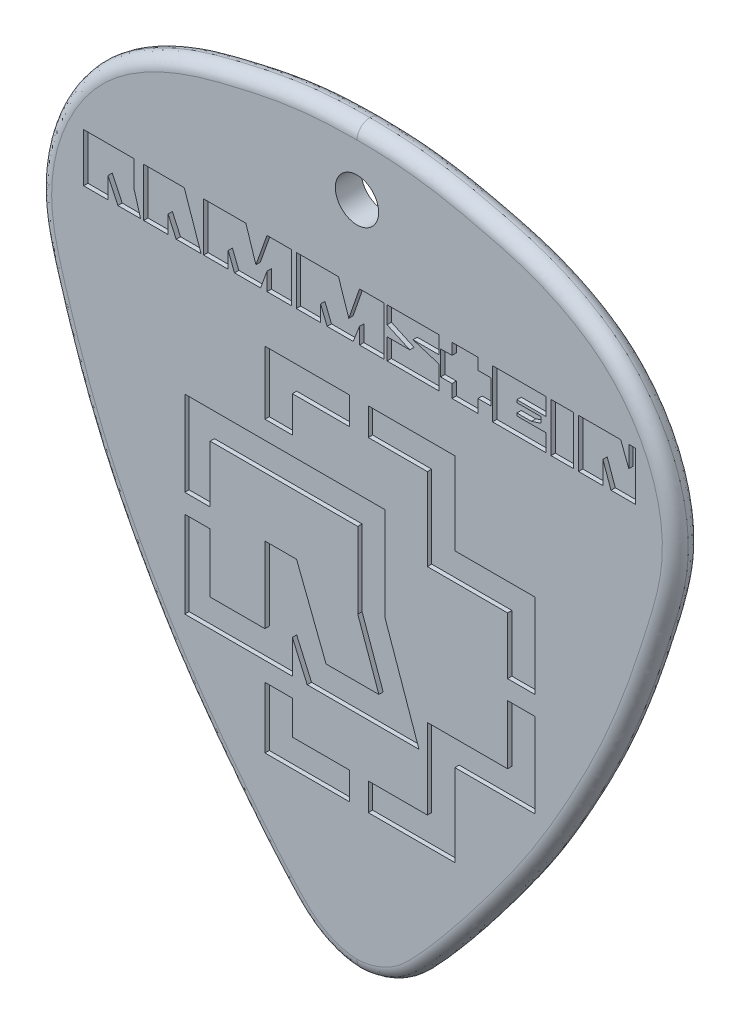
SolidWorks part; units mm, degrees
material "Nickel"
ref_plane "Front Plane" through (0, 0, 0) normal (0, 0, 1) x (1, 0, 0)
ref_plane "Top Plane" through (0, 0, 0) normal (0, 1, 0) x (1, 0, 0)
ref_plane "Right Plane" through (0, 0, 0) normal (1, 0, 0) x (0, 0, -1)
sketch "Sketch9" plane through (-49.9652, -1.9798, 0) normal (0, 0, 1) x (1, 0, 0)
  line L0 (49.9312, 18.5668) -> (49.9312, -17.1079) construction
  circle A1 centre (49.9312, 15.0287) radius 1
  spline S0 degree 3 poles (49.9312, 18.0287) (50.5822, 18.0238) (52.0435, 17.9887) (54.0305, 17.7033) (55.988, 17.2529) (58.0088, 16.7337) (60.0094, 15.8622) (62.6561, 14.0289) (64.4616, 11.0538) (64.7875, 7.3749) (63.9283, 4.4589) (62.9446, 1.4332) (61.7117, -1.5745) (60.1785, -4.5073) (58.5607, -7.295) (56.6435, -9.9646) (54.8628, -12.2747) (53.3893, -13.9945) (51.9899, -15.4429) (50.7935, -15.9421) (49.9312, -15.9653) knots 0 0 0 0 0.039894 0.08945 0.122624 0.162957 0.217169 0.255208 0.359361 0.416146 0.477175 0.543509 0.611614 0.675829 0.746189 0.80884 0.877031 0.924799 0.947638 1 1 1 1
  spline S1 degree 3 poles (49.9312, 18.0287) (49.2802, 18.0238) (47.819, 17.9887) (45.832, 17.7033) (43.8744, 17.2529) (41.8537, 16.7337) (39.853, 15.8622) (37.2063, 14.0289) (35.4008, 11.0538) (35.075, 7.3749) (35.9342, 4.4589) (36.9178, 1.4332) (38.1507, -1.5745) (39.684, -4.5073) (41.3018, -7.295) (43.219, -9.9646) (44.9997, -12.2747) (46.4731, -13.9945) (47.8725, -15.4429) (49.0689, -15.9421) (49.9312, -15.9653) knots 0 0 0 0 0.039894 0.08945 0.122624 0.162957 0.217169 0.255208 0.359361 0.416146 0.477175 0.543509 0.611614 0.675829 0.746189 0.80884 0.877031 0.924799 0.947638 1 1 1 1
  dimension "D1" = 2
  dimension "D2" = 3
extrude "mediator_2" add sketch "Sketch9" against normal blind 1.2 separate body
sketch "Sketch10" plane through (-49.9652, -1.9798, 0) normal (0, 0, 1) x (1, 0, 0)
  line L78 (101.711, 196.2021) -> (368.3776, 196.2021) construction
  line L79 (39.6213, 11.5287) -> (39.6213, 10.3368)
  line L80 (37.2943, 9.2785) -> (38.419, 9.2785)
  line L81 (37.2943, 9.2785) -> (37.2943, 11.5287)
  line L82 (37.2943, 11.5287) -> (39.6213, 11.5287)
  line L83 (62.7948, 9.2785) -> (62.7948, 11.5287)
  line L84 (39.6213, 10.3368) -> (39.9259, 9.2785)
  line L85 (38.419, 9.2785) -> (38.419, 10.2495)
  line L86 (38.419, 10.2495) -> (38.8771, 9.2785)
  line L87 (38.8771, 9.2785) -> (39.9259, 9.2785)
  line L88 (40.0704, 9.2785) -> (40.0704, 11.5287)
  line L89 (40.0704, 11.5287) -> (41.9447, 11.5287)
  line L90 (40.0704, 9.2785) -> (41.1994, 9.2785)
  line L91 (41.1994, 9.2785) -> (41.1994, 10.0986)
  line L92 (41.1994, 10.0986) -> (41.5727, 9.2785)
  line L93 (41.5727, 9.2785) -> (42.7203, 9.2785)
  line L94 (41.9447, 11.5287) -> (42.7203, 9.2785)
  line L95 (42.8452, 11.5287) -> (42.8452, 9.2785)
  line L96 (42.8452, 9.2785) -> (43.9744, 9.2785)
  line L97 (42.8452, 11.5287) -> (44.794, 11.5287)
  line L98 (46.8969, 11.5287) -> (46.8969, 9.2785)
  line L99 (47.1236, 9.2785) -> (47.1236, 11.5287)
  line L100 (47.1236, 11.5287) -> (49.0768, 11.5287)
  line L101 (47.1236, 9.2785) -> (48.2472, 9.2785)
  line L102 (51.1763, 11.5287) -> (51.1763, 9.2785)
  line L103 (51.3206, 9.2785) -> (51.3206, 10.2495)
  line L104 (51.3206, 11.5287) -> (53.725, 11.5287)
  line L105 (51.3206, 9.2785) -> (53.725, 9.2785)
  line L106 (53.725, 11.5287) -> (53.725, 10.7287)
  line L107 (55.52, 11.0032) -> (55.52, 11.5287)
  line L108 (53.7944, 11.0032) -> (54.3202, 11.0032)
  line L109 (53.7944, 11.0032) -> (53.7944, 9.8774)
  line L110 (53.7944, 9.8774) -> (54.3202, 9.8774)
  line L111 (56.1212, 11.0032) -> (56.1212, 9.8774)
  line L112 (54.3202, 9.2785) -> (55.52, 9.2785)
  line L113 (54.3202, 9.2785) -> (54.3202, 9.8774)
  line L114 (54.3202, 11.5287) -> (55.52, 11.5287)
  line L115 (55.52, 9.2785) -> (55.52, 9.8774)
  line L116 (54.3202, 11.0032) -> (54.3202, 11.5287)
  line L117 (55.52, 11.0032) -> (56.1212, 11.0032)
  line L118 (55.52, 9.8774) -> (56.1212, 9.8774)
  line L119 (54.3202, 11.5287) -> (55.52, 11.5287)
  line L120 (54.3202, 9.2785) -> (55.52, 9.2785)
  line L121 (43.9744, 9.2785) -> (43.9744, 10.0267)
  line L122 (43.9744, 10.0267) -> (44.2682, 9.2785)
  line L123 (45.7696, 9.2785) -> (45.7696, 10.0986)
  line L124 (45.7696, 10.0986) -> (45.4724, 9.2785)
  line L125 (44.2682, 9.2785) -> (45.4724, 9.2785)
  line L126 (45.7696, 9.2785) -> (46.8969, 9.2785)
  line L127 (44.794, 11.5287) -> (45.2581, 10.0986)
  line L128 (45.2581, 10.0986) -> (45.7696, 11.5287)
  line L129 (45.7696, 11.5287) -> (46.8969, 11.5287)
  line L130 (49.0768, 11.5287) -> (49.5501, 10.0986)
  line L131 (49.5501, 10.0986) -> (50.0466, 11.5287)
  line L132 (50.0466, 11.5287) -> (51.1763, 11.5287)
  line L133 (48.2472, 9.2785) -> (48.2472, 10.0267)
  line L134 (48.2472, 10.0267) -> (48.55, 9.2785)
  line L135 (48.55, 9.2785) -> (49.7528, 9.2785)
  line L136 (50.0466, 9.2785) -> (50.0466, 10.0267)
  line L137 (50.0466, 10.0267) -> (49.7528, 9.2785)
  line L138 (50.0466, 9.2785) -> (51.1763, 9.2785)
  line L139 (51.3206, 10.2495) -> (52.3702, 10.2495)
  line L140 (52.3702, 10.2495) -> (51.3206, 10.7287)
  line L141 (51.3206, 10.7287) -> (51.3206, 11.5287)
  line L142 (53.725, 10.7287) -> (52.5197, 10.7287)
  line L143 (52.5197, 10.7287) -> (53.725, 10.3544)
  line L144 (53.725, 10.3544) -> (53.725, 9.2785)
  line L145 (56.1952, 11.5287) -> (56.1952, 9.2785)
  line L146 (56.1952, 11.5287) -> (58.6695, 11.5287)
  line L147 (56.1952, 9.2785) -> (58.6695, 9.2785)
  line L148 (58.6695, 11.5287) -> (58.6695, 10.7287)
  line L149 (58.6695, 10.7287) -> (57.3202, 10.7287)
  line L150 (57.3202, 10.7287) -> (57.3202, 10.6087)
  line L151 (57.3202, 10.6087) -> (58.4448, 10.6087)
  line L152 (58.4448, 10.6087) -> (58.4448, 10.3486)
  line L153 (58.4448, 10.3486) -> (57.9949, 10.1985)
  line L154 (57.9949, 10.1985) -> (57.3189, 10.1985)
  line L155 (57.3189, 10.1985) -> (57.3189, 10.0785)
  line L156 (57.3189, 10.0785) -> (58.6695, 10.0785)
  line L157 (58.6695, 10.0785) -> (58.6695, 9.2785)
  line L158 (58.8938, 11.5287) -> (58.8938, 9.2785)
  line L159 (59.9445, 11.5287) -> (59.9445, 9.2785)
  line L160 (58.8938, 9.2785) -> (59.9445, 9.2785)
  line L161 (58.8938, 11.5287) -> (59.9445, 11.5287)
  line L162 (60.1688, 11.5287) -> (60.1688, 9.2785)
  line L163 (60.1688, 9.2785) -> (61.2951, 9.2785)
  line L164 (60.1688, 11.5287) -> (62.119, 11.5287)
  line L165 (62.4942, 11.5287) -> (62.4942, 10.5531)
  line L166 (62.4942, 10.5531) -> (62.119, 11.5287)
  line L167 (62.4942, 11.5287) -> (62.7948, 11.5287)
  line L168 (61.2951, 9.2785) -> (61.2951, 10.3281)
  line L169 (61.2951, 10.3281) -> (61.6698, 9.2785)
  line L170 (61.6698, 9.2785) -> (62.7948, 9.2785)
  circle A0 centre (49.9312, 15.0287) radius 1 construction
  dimension "D1" = 3.5
  dimension "D2" = 0.8
  dimension "D3" = 0.8
  dimension "D4" = 0.12
  dimension "D5" = 0.12
fillet "Fillet3" radius 0.6 4 edges
extrude "Rammstein" cut sketch "Sketch10" against normal blind 0.2 contours L86 L87 L84 L79 L82 L81 L80 L85 | L94 L89 L88 L90 L91 L92 L93 | L129 L128 L127 L97 L95 L96 L121 L122 L125 L124 L123 L126 L98 | L136 L138 L102 L132 L131 L130 L100 L99 L101 L133 L134 L135 L137 | L144 L143 L142 L106 L104 L141 L140 L139 L103 L105 | L115 L118 L111 L117 L107 L114 L116 L108 L109 L110 L113 L112 | L157 L156 L155 L154 L153 L152 L151 L150 L149 L148 L146 L145 L147 | L169 L170 L83 L167 L165 L166 L164 L162 L163 L168 | L158 L160 L159 L161 region at (-11.4729, 8.4341, 0) region at (11.4894, 8.4248, 0) region at (-8.7561, 8.3839, 0) region at (-5.1297, 8.3929, 0) region at (-0.8494, 8.3928, 0) region at (2.5644, 8.4143, 0) region at (4.9798, 8.4355, 0) region at (7.4056, 8.4248, 0)
sketch "Sketch11" plane through (0, 0, 0) normal (0, 0, 1) x (1, 0, 0)
  line L0 (25.7842, 90.0176) -> (159.1175, 90.0176) construction
  line L17 (-0.3902, 3.8019) -> (-3.0225, 3.8019)
  line L18 (-4.2901, 2.1447) -> (-3.0225, 2.1447)
  line L19 (-4.2901, 2.1447) -> (-4.2901, 5.0698)
  line L20 (-4.2901, 5.0698) -> (-0.3902, 5.0698)
  line L21 (-0.3902, 3.8019) -> (-0.3902, 5.0698)
  line L22 (-3.0225, 3.8019) -> (-3.0225, 2.1447)
  line L23 (0.4867, 3.8019) -> (3.2168, 3.8019)
  line L24 (8.19, -2.6327) -> (6.9237, -2.6327)
  line L25 (8.19, -2.6327) -> (8.19, 1.2674)
  line L26 (4.4865, 5.0698) -> (0.4867, 5.0698)
  line L27 (0.4867, 3.8019) -> (0.4867, 5.0698)
  line L28 (3.2168, 3.8019) -> (3.2168, 0)
  line L29 (3.2168, 0) -> (6.9237, 0)
  line L30 (6.9237, 0) -> (6.9237, -2.6327)
  line L31 (8.19, 1.2674) -> (4.4865, 1.2674)
  line L32 (4.4865, 1.2674) -> (4.4865, 5.0698)
  line L33 (8.19, -3.511) -> (8.19, -7.4102)
  line L34 (8.19, -7.4102) -> (4.4865, -7.4102)
  line L35 (4.4865, -7.4102) -> (4.4865, -11.2134)
  line L36 (4.4865, -11.2134) -> (0.4873, -11.2134)
  line L37 (0.4873, -11.2134) -> (0.4873, -9.945)
  line L38 (0.4873, -9.945) -> (3.2173, -9.945)
  line L39 (3.2173, -9.945) -> (3.2173, -6.2391)
  line L40 (3.2173, -6.2391) -> (6.9237, -6.2391)
  line L41 (6.9237, -6.2391) -> (6.9237, -3.511)
  line L42 (6.9237, -3.511) -> (8.19, -3.511)
  line L43 (-4.2901, -8.385) -> (-4.2901, -11.2134)
  line L44 (-4.2901, -11.2134) -> (-0.3902, -11.2134)
  line L45 (-0.3902, -11.2134) -> (-0.3902, -9.945)
  line L46 (-0.3902, -9.945) -> (-3.0225, -9.945)
  line L47 (-3.0225, -9.945) -> (-3.0225, -8.385)
  line L48 (-3.0225, -8.385) -> (-4.2901, -8.385)
  line L49 (-7.9951, -2.6327) -> (-6.8231, -2.6327)
  line L50 (-7.9951, 1.2989) -> (1.269, 1.2989)
  line L51 (-7.9951, 1.2989) -> (-7.9951, -2.6327)
  line L52 (-7.9951, -7.5074) -> (-3.0225, -7.5074)
  line L54 (-6.8231, -2.6327) -> (-6.8231, 0)
  line L55 (-6.8231, 0) -> (0, 0)
  line L56 (0, 0) -> (0, -3.511)
  line L57 (0, -3.511) -> (0.975, -6.2391)
  line L58 (-7.9951, -3.511) -> (-6.8231, -3.511)
  line L59 (-6.8231, -3.511) -> (-6.8231, -6.2391)
  line L60 (-6.8231, -6.2391) -> (-4.2901, -6.2391)
  line L61 (-4.2901, -6.2391) -> (-4.2901, -2.7299)
  line L62 (-4.2901, -2.7299) -> (-2.8275, -2.7299)
  line L63 (-2.8275, -2.7299) -> (-1.4654, -6.2391)
  line L64 (-1.4654, -6.2391) -> (0.975, -6.2391)
  line L65 (1.269, 1.2989) -> (1.269, -3.0527)
  line L66 (1.269, -3.0527) -> (2.8295, -7.5074)
  line L67 (-3.0225, -7.5074) -> (-3.0225, -5.9535)
  line L68 (-3.0225, -5.9535) -> (-2.3359, -7.5074)
  line L69 (-2.3359, -7.5074) -> (2.8295, -7.5074)
  line L70 (-7.9951, -3.511) -> (-7.9951, -7.5074)
  line L71 (0, 0) -> (0, 19.7504) construction
  line L72 (0, 0) -> (15.2231, 0) construction
  dimension "D1" = 1.9479
  dimension "D2" = 0.8769
  dimension "D3" = 0.8776
  dimension "D4" = 0.8783
extrude "Logo" cut sketch "Sketch11" against normal blind 0.2
